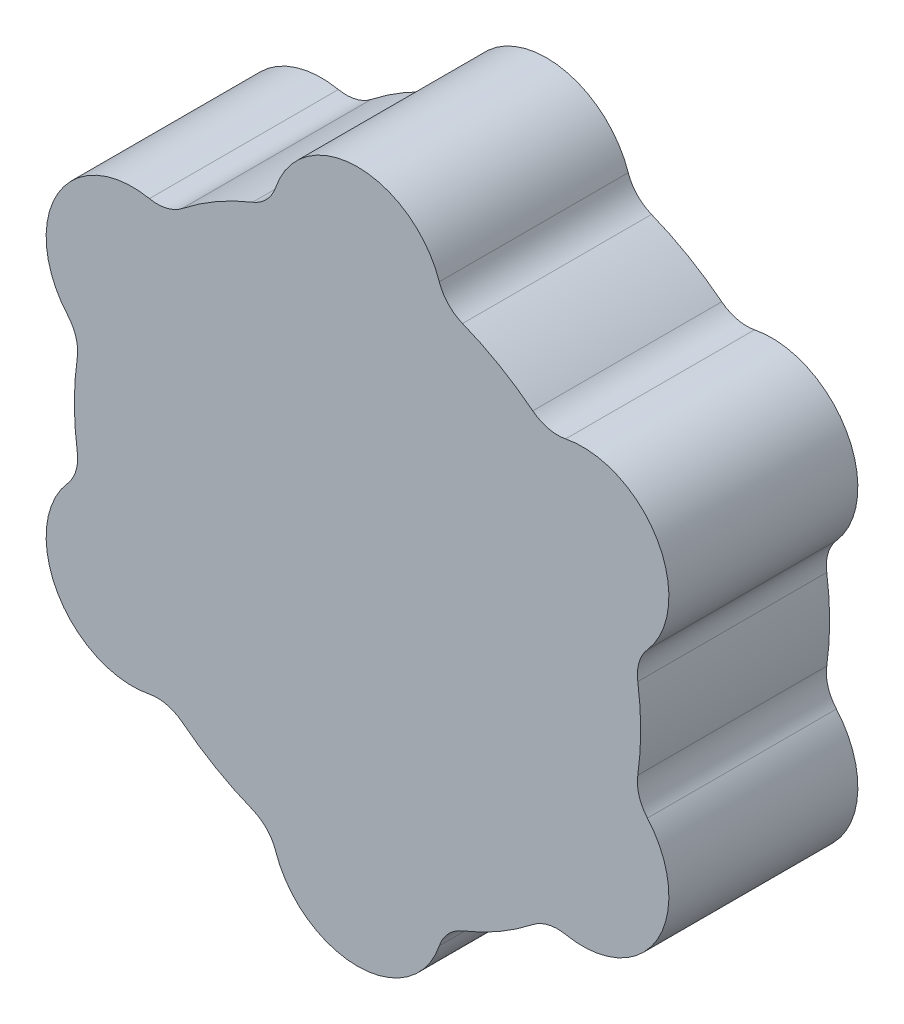
SolidWorks part; units mm, degrees
ref_plane "Front Plane" through (0, 0, 0) normal (0, 0, 1) x (1, 0, 0)
ref_plane "Top Plane" through (0, 0, 0) normal (0, 1, 0) x (1, 0, 0)
ref_plane "Right Plane" through (0, 0, 0) normal (1, 0, 0) x (0, 0, -1)
sketch "Sketch5" plane through (0, 0, 0) normal (0, 0, 1) x (1, 0, 0)
  line L0 (0, 0) -> (0, 13.0969) construction
  circle A0 centre (0, 0) radius 14.2748
  circle A1 centre (0, 0) radius 17.4498 construction
  arc A2 (-4.3232, 13.6044) -> (4.3232, 13.6044) centre (0, 13.0969) cw
  arc A3 (9.6201, 10.5462) -> (13.9434, 3.0582) centre (11.3422, 6.5484) cw
  arc A4 (13.9434, -3.0582) -> (9.6201, -10.5462) centre (11.3422, -6.5484) cw
  arc A5 (4.3232, -13.6044) -> (-4.3232, -13.6044) centre (0, -13.0969) cw
  arc A6 (-9.6201, -10.5462) -> (-13.9434, -3.0582) centre (-11.3422, -6.5484) cw
  arc A7 (-13.9434, 3.0582) -> (-9.6201, 10.5462) centre (-11.3422, 6.5484) cw
  point P24 (0, 0)
  dimension "D1" = 28.5496
  dimension "D2" = 34.8996
  dimension "D3" = 4.3529
  dimension "D4" = 6
extrude "Boss-Extrude2" add sketch "Sketch5" along normal blind 9.525 contours A7 A0 | A2 A0 | A3 A0 | A4 A0 | A5 A0 | A6 A0 | A0 region at (13.3933, 7.7326, 0) region at (13.3933, -7.7326, 0) region at (0, 15.4653, 0) region at (0, -15.4653, 0) region at (-13.3933, 7.7326, 0) region at (-13.3933, -7.7326, 0)
fillet "Fillet1" radius 2.032 12 edges at (-9.6201, 10.5462, 4.7625) (-4.3232, 13.6044, 4.7625) (4.3232, 13.6044, 4.7625) (9.6201, 10.5462, 4.7625) (13.9434, 3.0582, 4.7625) (13.9434, -3.0582, 4.7625) (9.6201, -10.5462, 4.7625) (4.3232, -13.6044, 4.7625) (-4.3232, -13.6044, 4.7625) (-9.6201, -10.5462, 4.7625) (-13.9434, -3.0582, 4.7625) (-13.9434, 3.0582, 4.7625)
